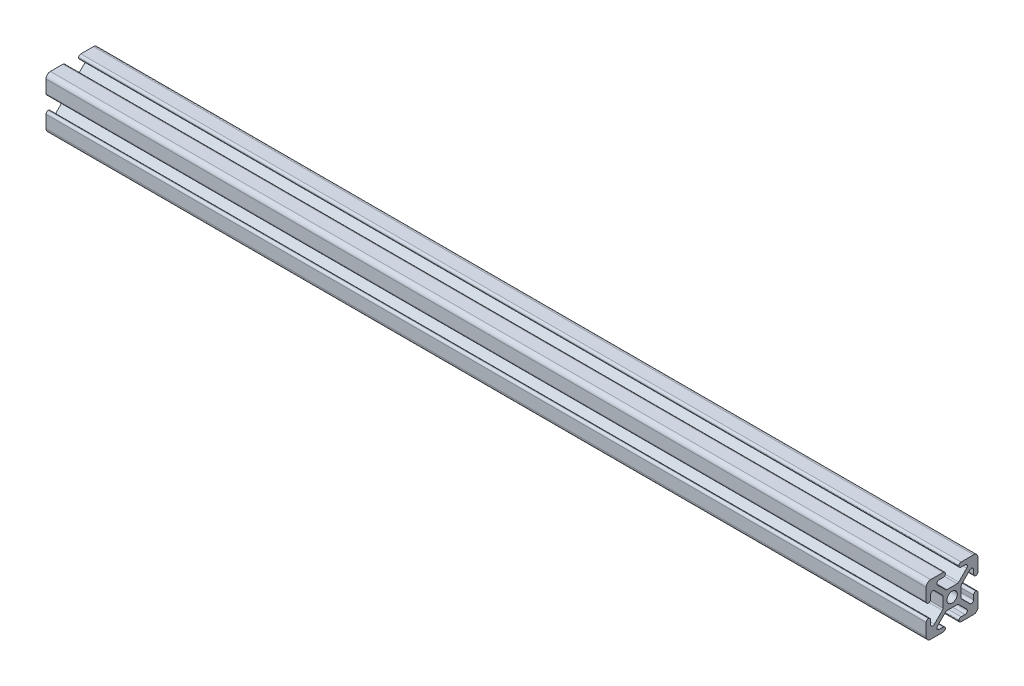
SolidWorks part; units mm, degrees
ref_plane "Front Plane" through (0, 0, 0) normal (1, 0, 0) x (0, 1, 0)
ref_plane "Top Plane" through (0, 0, 0) normal (0, 0, 1) x (0, 1, 0)
ref_plane "Right Plane" through (0, 0, 0) normal (0, 1, 0) x (-1, 0, 0)
sketch "Sketch1" plane through (0, 0, 0) normal (1, 0, 0) x (0, 1, 0)
  line L0 (0, 0) -> (0, 12.5) construction
  line L1 (-12.5, -12.5) -> (12.5, -12.5)
  line L2 (-12.5, -12.5) -> (-12.5, 12.5)
  line L3 (-12.5, 12.5) -> (12.5, 12.5)
  line L4 (12.5, -12.5) -> (12.5, 12.5)
  line L5 (-12.5, -12.5) -> (12.5, 12.5) construction
  line L6 (-12.5, 12.5) -> (12.5, -12.5) construction
  line L7 (-3.25, 12.5) -> (-3.25, 10.37)
  line L8 (-3.25, 10.37) -> (-8.8639, 10.37)
  line L9 (-8.8639, 10.37) -> (-2.8739, 4.38)
  line L10 (-2.8739, 4.38) -> (2.8739, 4.38)
  line L11 (8.8639, 10.37) -> (2.8739, 4.38)
  line L12 (3.25, 10.37) -> (8.8639, 10.37)
  line L13 (3.25, 12.5) -> (3.25, 10.37)
  line L14 (12.5, -3.25) -> (10.37, -3.25)
  line L15 (10.37, -3.25) -> (10.37, -8.8639)
  line L16 (10.37, -8.8639) -> (4.38, -2.8739)
  line L17 (4.38, 2.8739) -> (4.38, -2.8739)
  line L18 (10.37, 8.8639) -> (4.38, 2.8739)
  line L19 (10.37, 3.25) -> (10.37, 8.8639)
  line L20 (12.5, 3.25) -> (10.37, 3.25)
  line L21 (-3.25, -12.5) -> (-3.25, -10.37)
  line L22 (-3.25, -10.37) -> (-8.8639, -10.37)
  line L23 (-8.8639, -10.37) -> (-2.8739, -4.38)
  line L24 (2.8739, -4.38) -> (-2.8739, -4.38)
  line L25 (8.8639, -10.37) -> (2.8739, -4.38)
  line L26 (3.25, -10.37) -> (8.8639, -10.37)
  line L27 (3.25, -12.5) -> (3.25, -10.37)
  line L28 (-12.5, 3.25) -> (-10.37, 3.25)
  line L29 (-10.37, 3.25) -> (-10.37, 8.8639)
  line L30 (-10.37, 8.8639) -> (-4.38, 2.8739)
  line L31 (-4.38, -2.8739) -> (-4.38, 2.8739)
  line L32 (-10.37, -8.8639) -> (-4.38, -2.8739)
  line L33 (-10.37, -3.25) -> (-10.37, -8.8639)
  line L34 (-12.5, -3.25) -> (-10.37, -3.25)
  circle A0 centre (0, 0) radius 2.5
  point P0 (0, 0)
  point P15 (0, 4.38)
  dimension "D3" = 5
  dimension "D1" = 25
  dimension "D2" = 25
  dimension "D4" = 2.13
  dimension "D5" = 2.13
  dimension "D6" = 6.5
  dimension "D7" = 4.38
  dimension "D8" = 4
extrude "Boss-Extrude1" add sketch "Sketch1" along normal blind 425 contours L34 L2 L1 L21 L22 L23 L24 L25 L26 L27 L4 L14 L15 L16 L17 L18 L19 L20 L3 L13 L12 L11 L10 L9 L8 L7 L28 L29 L30 L31 L32 L33 A0 region at (0, -12.1464, -7.875)
fillet "Fillet1" radius 1.065 32 edges at (212.5, -10.37, -8.8639) (212.5, 2.8739, -4.38) (212.5, -2.8739, -4.38) (212.5, -4.38, 2.8739) (212.5, -4.38, -2.8739) (212.5, -2.8739, 4.38) (212.5, 2.8739, 4.38) (212.5, 4.38, 2.8739) (212.5, 4.38, -2.8739) (212.5, -8.8639, -10.37) (212.5, 8.8639, -10.37) (212.5, 10.37, -8.8639) (212.5, -10.37, 8.8639) (212.5, -8.8639, 10.37) (212.5, 10.37, 8.8639) (212.5, 8.8639, 10.37) (212.5, 12.5, 3.25) (212.5, -3.25, -12.5) (212.5, -10.37, 3.25) (212.5, 10.37, 3.25) (212.5, -10.37, -3.25) (212.5, -12.5, -3.25) (212.5, -12.5, 3.25) (212.5, 3.25, -10.37) (212.5, -3.25, -10.37) (212.5, 3.25, -12.5) (212.5, 10.37, -3.25) (212.5, 12.5, -3.25) (212.5, 3.25, 12.5) (212.5, 3.25, 10.37) (212.5, -3.25, 10.37) (212.5, -3.25, 12.5)
fillet "Fillet2" radius 2.13 4 edges at (212.5, 12.5, -12.5) (212.5, -12.5, -12.5) (212.5, 12.5, 12.5) (212.5, -12.5, 12.5)
sketch "Sketch2" plane through (425, 0, 0) normal (1, 0, 0) x (0, 1, 0)
  line L0 (10.37, -12.5) -> (4.315, -12.5)
  line L1 (10.37, -12.5) -> (4.315, -12.5)
  line L2 (4.315, -10.37) -> (6.2927, -10.37)
  line L3 (4.315, -10.37) -> (6.2927, -10.37)
  line L4 (7.0458, -8.5519) -> (3.1858, -4.6919)
  line L5 (7.0458, -8.5519) -> (3.1858, -4.6919)
  line L6 (2.4327, -4.38) -> (-2.4327, -4.38)
  line L7 (2.4327, -4.38) -> (-2.4327, -4.38)
  line L8 (-3.1858, -4.6919) -> (-7.0458, -8.5519)
  line L9 (-3.1858, -4.6919) -> (-7.0458, -8.5519)
  line L10 (-6.2927, -10.37) -> (-4.315, -10.37)
  line L11 (-6.2927, -10.37) -> (-4.315, -10.37)
  line L12 (-4.315, -12.5) -> (-10.37, -12.5)
  line L13 (-4.315, -12.5) -> (-10.37, -12.5)
  line L14 (-12.5, -10.37) -> (-12.5, -4.315)
  line L15 (-12.5, -10.37) -> (-12.5, -4.315)
  line L16 (-10.37, -4.315) -> (-10.37, -6.2927)
  line L17 (-10.37, -4.315) -> (-10.37, -6.2927)
  line L18 (-8.5519, -7.0458) -> (-4.6919, -3.1858)
  line L19 (-8.5519, -7.0458) -> (-4.6919, -3.1858)
  line L20 (-4.38, -2.4327) -> (-4.38, 2.4327)
  line L21 (-4.38, -2.4327) -> (-4.38, 2.4327)
  line L22 (-4.6919, 3.1858) -> (-8.5519, 7.0458)
  line L23 (-4.6919, 3.1858) -> (-8.5519, 7.0458)
  line L24 (-10.37, 6.2927) -> (-10.37, 4.315)
  line L25 (-10.37, 6.2927) -> (-10.37, 4.315)
  line L26 (-12.5, 4.315) -> (-12.5, 10.37)
  line L27 (-12.5, 4.315) -> (-12.5, 10.37)
  line L28 (-10.37, 12.5) -> (-4.315, 12.5)
  line L29 (-10.37, 12.5) -> (-4.315, 12.5)
  line L30 (-4.315, 10.37) -> (-6.2927, 10.37)
  line L31 (-4.315, 10.37) -> (-6.2927, 10.37)
  line L32 (-7.0458, 8.5519) -> (-3.1858, 4.6919)
  line L33 (-7.0458, 8.5519) -> (-3.1858, 4.6919)
  line L34 (-2.4327, 4.38) -> (2.4327, 4.38)
  line L35 (-2.4327, 4.38) -> (2.4327, 4.38)
  line L36 (3.1858, 4.6919) -> (7.0458, 8.5519)
  line L37 (3.1858, 4.6919) -> (7.0458, 8.5519)
  line L38 (6.2927, 10.37) -> (4.315, 10.37)
  line L39 (6.2927, 10.37) -> (4.315, 10.37)
  line L40 (4.315, 12.5) -> (10.37, 12.5)
  line L41 (4.315, 12.5) -> (10.37, 12.5)
  line L42 (12.5, 10.37) -> (12.5, 4.315)
  line L43 (12.5, 10.37) -> (12.5, 4.315)
  line L44 (10.37, 4.315) -> (10.37, 6.2927)
  line L45 (10.37, 4.315) -> (10.37, 6.2927)
  line L46 (8.5519, 7.0458) -> (4.6919, 3.1858)
  line L47 (8.5519, 7.0458) -> (4.6919, 3.1858)
  line L48 (4.38, 2.4327) -> (4.38, -2.4327)
  line L49 (4.38, 2.4327) -> (4.38, -2.4327)
  line L50 (4.6919, -3.1858) -> (8.5519, -7.0458)
  line L51 (4.6919, -3.1858) -> (8.5519, -7.0458)
  line L52 (10.37, -6.2927) -> (10.37, -4.315)
  line L53 (10.37, -6.2927) -> (10.37, -4.315)
  line L54 (12.5, -4.315) -> (12.5, -10.37)
  line L55 (12.5, -4.315) -> (12.5, -10.37)
  arc A0 (10.37, -12.5) -> (12.5, -10.37) centre (10.37, -10.37) ccw
  circle A1 centre (0, 0) radius 2.5
  circle A2 centre (0, 0) radius 2.5
  arc A3 (10.37, -12.5) -> (12.5, -10.37) centre (10.37, -10.37) ccw
  arc A4 (3.25, -11.435) -> (4.315, -12.5) centre (4.315, -11.435) ccw
  arc A5 (3.25, -11.435) -> (4.315, -12.5) centre (4.315, -11.435) ccw
  arc A6 (4.315, -10.37) -> (3.25, -11.435) centre (4.315, -11.435) ccw
  arc A7 (4.315, -10.37) -> (3.25, -11.435) centre (4.315, -11.435) ccw
  arc A8 (6.2927, -10.37) -> (7.0458, -8.5519) centre (6.2927, -9.305) ccw
  arc A9 (6.2927, -10.37) -> (7.0458, -8.5519) centre (6.2927, -9.305) ccw
  arc A10 (3.1858, -4.6919) -> (2.4327, -4.38) centre (2.4327, -5.445) ccw
  arc A11 (3.1858, -4.6919) -> (2.4327, -4.38) centre (2.4327, -5.445) ccw
  arc A12 (-2.4327, -4.38) -> (-3.1858, -4.6919) centre (-2.4327, -5.445) ccw
  arc A13 (-2.4327, -4.38) -> (-3.1858, -4.6919) centre (-2.4327, -5.445) ccw
  arc A14 (-7.0458, -8.5519) -> (-6.2927, -10.37) centre (-6.2927, -9.305) ccw
  arc A15 (-7.0458, -8.5519) -> (-6.2927, -10.37) centre (-6.2927, -9.305) ccw
  arc A16 (-3.25, -11.435) -> (-4.315, -10.37) centre (-4.315, -11.435) ccw
  arc A17 (-3.25, -11.435) -> (-4.315, -10.37) centre (-4.315, -11.435) ccw
  arc A18 (-4.315, -12.5) -> (-3.25, -11.435) centre (-4.315, -11.435) ccw
  arc A19 (-4.315, -12.5) -> (-3.25, -11.435) centre (-4.315, -11.435) ccw
  arc A20 (-12.5, -10.37) -> (-10.37, -12.5) centre (-10.37, -10.37) ccw
  arc A21 (-12.5, -10.37) -> (-10.37, -12.5) centre (-10.37, -10.37) ccw
  arc A22 (-11.435, -3.25) -> (-12.5, -4.315) centre (-11.435, -4.315) ccw
  arc A23 (-11.435, -3.25) -> (-12.5, -4.315) centre (-11.435, -4.315) ccw
  arc A24 (-10.37, -4.315) -> (-11.435, -3.25) centre (-11.435, -4.315) ccw
  arc A25 (-10.37, -4.315) -> (-11.435, -3.25) centre (-11.435, -4.315) ccw
  arc A26 (-10.37, -6.2927) -> (-8.5519, -7.0458) centre (-9.305, -6.2927) ccw
  arc A27 (-10.37, -6.2927) -> (-8.5519, -7.0458) centre (-9.305, -6.2927) ccw
  arc A28 (-4.6919, -3.1858) -> (-4.38, -2.4327) centre (-5.445, -2.4327) ccw
  arc A29 (-4.6919, -3.1858) -> (-4.38, -2.4327) centre (-5.445, -2.4327) ccw
  arc A30 (-4.38, 2.4327) -> (-4.6919, 3.1858) centre (-5.445, 2.4327) ccw
  arc A31 (-4.38, 2.4327) -> (-4.6919, 3.1858) centre (-5.445, 2.4327) ccw
  arc A32 (-8.5519, 7.0458) -> (-10.37, 6.2927) centre (-9.305, 6.2927) ccw
  arc A33 (-8.5519, 7.0458) -> (-10.37, 6.2927) centre (-9.305, 6.2927) ccw
  arc A34 (-11.435, 3.25) -> (-10.37, 4.315) centre (-11.435, 4.315) ccw
  arc A35 (-11.435, 3.25) -> (-10.37, 4.315) centre (-11.435, 4.315) ccw
  arc A36 (-12.5, 4.315) -> (-11.435, 3.25) centre (-11.435, 4.315) ccw
  arc A37 (-12.5, 4.315) -> (-11.435, 3.25) centre (-11.435, 4.315) ccw
  arc A38 (-10.37, 12.5) -> (-12.5, 10.37) centre (-10.37, 10.37) ccw
  arc A39 (-10.37, 12.5) -> (-12.5, 10.37) centre (-10.37, 10.37) ccw
  arc A40 (-3.25, 11.435) -> (-4.315, 12.5) centre (-4.315, 11.435) ccw
  arc A41 (-3.25, 11.435) -> (-4.315, 12.5) centre (-4.315, 11.435) ccw
  arc A42 (-4.315, 10.37) -> (-3.25, 11.435) centre (-4.315, 11.435) ccw
  arc A43 (-4.315, 10.37) -> (-3.25, 11.435) centre (-4.315, 11.435) ccw
  arc A44 (-6.2927, 10.37) -> (-7.0458, 8.5519) centre (-6.2927, 9.305) ccw
  arc A45 (-6.2927, 10.37) -> (-7.0458, 8.5519) centre (-6.2927, 9.305) ccw
  arc A46 (-3.1858, 4.6919) -> (-2.4327, 4.38) centre (-2.4327, 5.445) ccw
  arc A47 (-3.1858, 4.6919) -> (-2.4327, 4.38) centre (-2.4327, 5.445) ccw
  arc A48 (2.4327, 4.38) -> (3.1858, 4.6919) centre (2.4327, 5.445) ccw
  arc A49 (2.4327, 4.38) -> (3.1858, 4.6919) centre (2.4327, 5.445) ccw
  arc A50 (7.0458, 8.5519) -> (6.2927, 10.37) centre (6.2927, 9.305) ccw
  arc A51 (7.0458, 8.5519) -> (6.2927, 10.37) centre (6.2927, 9.305) ccw
  arc A52 (3.25, 11.435) -> (4.315, 10.37) centre (4.315, 11.435) ccw
  arc A53 (3.25, 11.435) -> (4.315, 10.37) centre (4.315, 11.435) ccw
  arc A54 (4.315, 12.5) -> (3.25, 11.435) centre (4.315, 11.435) ccw
  arc A55 (4.315, 12.5) -> (3.25, 11.435) centre (4.315, 11.435) ccw
  arc A56 (12.5, 10.37) -> (10.37, 12.5) centre (10.37, 10.37) ccw
  arc A57 (12.5, 10.37) -> (10.37, 12.5) centre (10.37, 10.37) ccw
  arc A58 (11.435, 3.25) -> (12.5, 4.315) centre (11.435, 4.315) ccw
  arc A59 (11.435, 3.25) -> (12.5, 4.315) centre (11.435, 4.315) ccw
  arc A60 (10.37, 4.315) -> (11.435, 3.25) centre (11.435, 4.315) ccw
  arc A61 (10.37, 4.315) -> (11.435, 3.25) centre (11.435, 4.315) ccw
  arc A62 (10.37, 6.2927) -> (8.5519, 7.0458) centre (9.305, 6.2927) ccw
  arc A63 (10.37, 6.2927) -> (8.5519, 7.0458) centre (9.305, 6.2927) ccw
  arc A64 (4.6919, 3.1858) -> (4.38, 2.4327) centre (5.445, 2.4327) ccw
  arc A65 (4.6919, 3.1858) -> (4.38, 2.4327) centre (5.445, 2.4327) ccw
  arc A66 (4.38, -2.4327) -> (4.6919, -3.1858) centre (5.445, -2.4327) ccw
  arc A67 (4.38, -2.4327) -> (4.6919, -3.1858) centre (5.445, -2.4327) ccw
  arc A68 (8.5519, -7.0458) -> (10.37, -6.2927) centre (9.305, -6.2927) ccw
  arc A69 (8.5519, -7.0458) -> (10.37, -6.2927) centre (9.305, -6.2927) ccw
  arc A70 (11.435, -3.25) -> (10.37, -4.315) centre (11.435, -4.315) ccw
  arc A71 (11.435, -3.25) -> (10.37, -4.315) centre (11.435, -4.315) ccw
  arc A72 (12.5, -4.315) -> (11.435, -3.25) centre (11.435, -4.315) ccw
  arc A73 (12.5, -4.315) -> (11.435, -3.25) centre (11.435, -4.315) ccw
  dimension "D1" = 0
